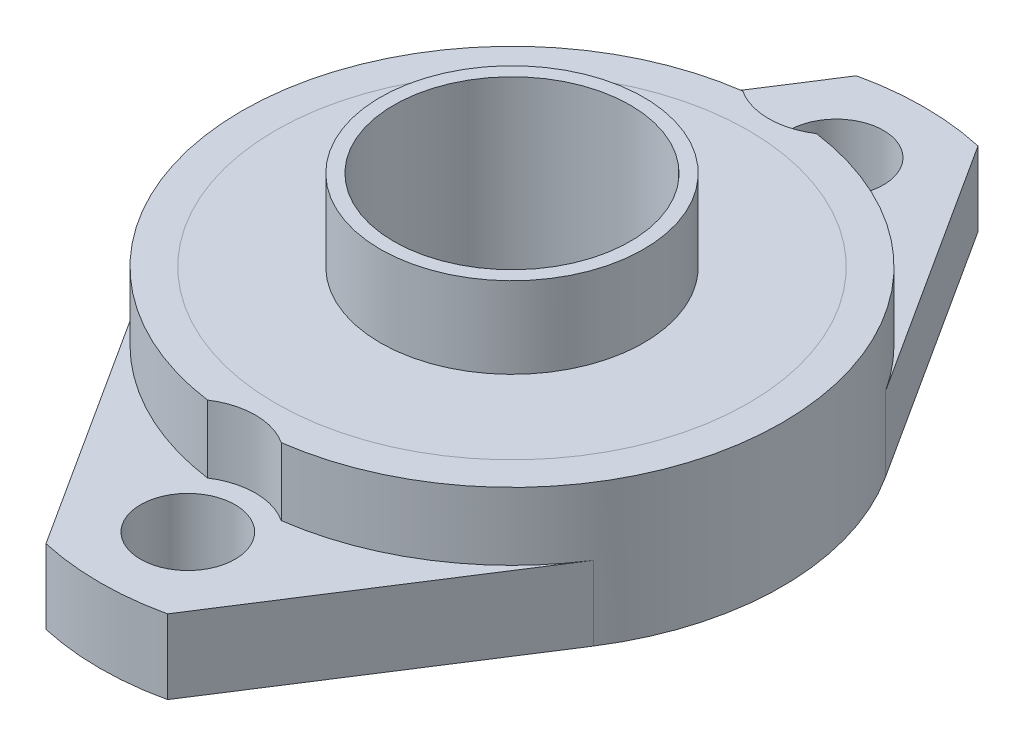
SolidWorks part; units mm, degrees
ref_plane "Front Plane" through (0, 0, 0) normal (0, 0, 1) x (1, 0, 0)
ref_plane "Top Plane" through (0, 0, 0) normal (0, 1, 0) x (1, 0, 0)
ref_plane "Right Plane" through (0, 0, 0) normal (1, 0, 0) x (0, 0, -1)
sketch "Sketch1" plane through (0, 0, 0) normal (0, 1, 0) x (1, 0, 0)
  line L0 (0, 0) -> (0, 61) construction
  line L1 (-33.6548, 21.6185) -> (-9, 60)
  line L2 (0, 61) -> (-33.6548, 61) construction
  line L3 (0, 0) -> (-40, 0) construction
  line L4 (33.6548, 21.6185) -> (9, 60)
  line L5 (33.6548, -21.6185) -> (9, -60)
  line L6 (-33.6548, -21.6185) -> (-9, -60)
  arc A0 (-5.4644, 39.625) -> (-5.4644, -39.625) centre (0, 0) ccw
  circle A1 centre (0, 0) radius 35
  arc A2 (-9, 60) -> (9, 60) centre (0, 20) cw
  circle A3 centre (0, 48) radius 7
  arc A4 (-5.4644, 39.625) -> (5.4644, 39.625) centre (0, 48) ccw
  circle A5 centre (0, 0) radius 40 construction
  arc A6 (-5.4644, -39.625) -> (5.4644, -39.625) centre (0, -48) cw
  circle A7 centre (0, -48) radius 7
  arc A8 (-9, -60) -> (9, -60) centre (0, -20) ccw
  arc A9 (5.4644, -39.625) -> (5.4644, 39.625) centre (0, 0) ccw
  point P1 (0, 0)
  point P18 (0, 0)
  point P28 (0, 0)
  point P29 (-34.7248, 19.8542)
  point P30 (-7.8078, 60)
  point P31 (-10.2023, 60)
  dimension "D1" = 80
  dimension "D4" = 122
  dimension "D5" = 14
  dimension "D8" = 3
  dimension "D3" = 18
  dimension "D7" = 96
  dimension "D9" = 60
  dimension "D2" = 5
extrude "Boss-Extrude1" add sketch "Sketch1" along normal blind 11 contours A9 L4 A2 L1 A0 A4 A3 | A6 A9 A4 A0 A1 | A9 A6 A0 L6 A8 L5 A7 region at (-20.6712, 0, -40.3878) region at (-20.926, 0, -32.761) region at (-21.952, 0, 34.3672)
sketch "Sketch2" plane through (0, 11, 0) normal (0, 1, 0) x (1, 0, 0)
  circle A0 centre (0, 0) radius 40
  circle A1 centre (0, 0) radius 35
  circle A2 centre (0, 0) radius 35 construction
  arc A3 (33.6548, -21.6185) -> (33.6548, 21.6185) centre (0, 0) ccw construction
extrude "Boss-Extrude2" add sketch "Sketch2" along normal blind 10
sketch "Sketch3" plane through (0, 21, 0) normal (0, 1, 0) x (1, 0, 0)
  circle A0 centre (0, 48) radius 10
  circle A1 centre (0, -48) radius 10
  circle A2 centre (0, 48) radius 7 construction
  dimension "D1" = 3
extrude "Cut-Extrude1" cut sketch "Sketch3" against normal up to surface (10 mm away) up to face at (0, 11, 45.6546)
sketch "Sketch4" plane through (0, 21, 0) normal (0, 1, 0) x (1, 0, 0)
  circle A0 centre (0, 0) radius 35
  circle A1 centre (0, 0) radius 19.5
  circle A2 centre (0, 0) radius 35 construction
  dimension "D1" = 39
extrude "Boss-Extrude3" add sketch "Sketch4" against normal up to surface (21 mm away) separate body up to face at (0, 0, 0)
sketch "Sketch5" plane through (0, 21, 0) normal (0, 1, 0) x (1, 0, 0)
  circle A0 centre (0, 0) radius 19.5
  circle A1 centre (0, 0) radius 17.5
  circle A2 centre (0, 0) radius 19.5 construction
  dimension "D1" = 35
extrude "Boss-Extrude4" add sketch "Sketch5" along normal blind 12 and the other way up to surface (21 mm away) separate body other way up to face at (0, 0, 35)
sketch "Sketch6" plane through (0, 0, 0) normal (0, -1, 0) x (-1, 0, 0)
  circle A0 centre (0, 0) radius 35
  circle A1 centre (0, 0) radius 35 construction
extrude "Cut-Extrude2" cut sketch "Sketch6" against normal blind 3
